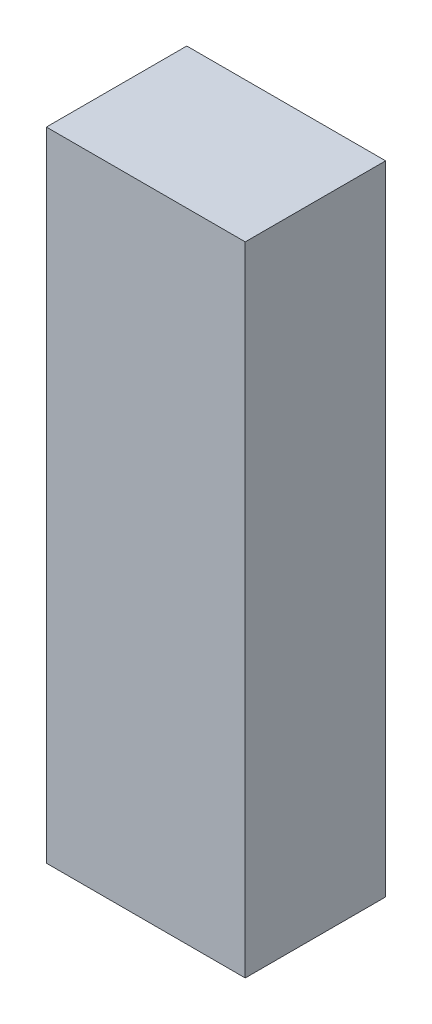
SolidWorks part; units mm, degrees
ref_plane "Front Plane" through (0, 0, 0) normal (0, 0, 1) x (1, 0, 0)
ref_plane "Top Plane" through (0, 0, 0) normal (0, 1, 0) x (1, 0, 0)
ref_plane "Right Plane" through (0, 0, 0) normal (1, 0, 0) x (0, 0, -1)
sketch "Sketch1" plane through (0, 0, 0) normal (0, 0, 1) x (1, 0, 0)
  line L1 (-313.7492, 0) -> (-279.7492, 0)
  line L2 (-313.7492, 0) -> (-313.7492, 109)
  line L3 (-313.7492, 109) -> (-279.7492, 109)
  line L4 (-279.7492, 0) -> (-279.7492, 109)
  dimension "D1" = 34
  dimension "D2" = 109
extrude "Boss-Extrude1" add sketch "Sketch1" along normal blind 24
